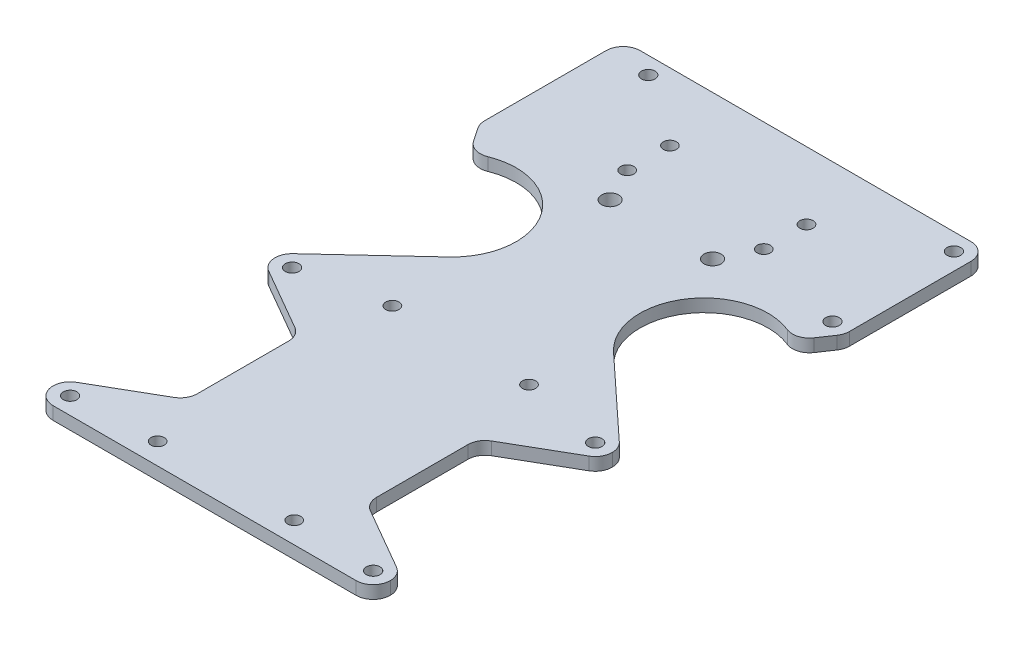
SolidWorks part; units mm, degrees
material "Thornel Mat VMA"
ref_plane "Front Plane" through (0, 0, 0) normal (0, 0, 1) x (1, 0, 0)
ref_plane "Top Plane" through (0, 0, 0) normal (0, 1, 0) x (1, 0, 0)
ref_plane "Right Plane" through (0, 0, 0) normal (1, 0, 0) x (0, 0, -1)
sketch "Sketch1" plane through (0, 0, 0) normal (0, 1, 0) x (1, 0, 0)
  line L0 (0, 0) -> (0, -82.5) construction
  line L1 (29.5, 0) -> (0, 0) construction
  line L19 (16, -27.5) -> (-16, -27.5) construction
  line L22 (16, -27.5) -> (16, 27.5) construction
  line L25 (16, 27.5) -> (-16, 27.5) construction
  line L28 (-16, -27.5) -> (-16, 27.5) construction
  line L38 (16, -27.5) -> (-16, 27.5) construction
  line L41 (47.5, 62.5) -> (-47.5, 62.5)
  line L44 (47.5, 62.5) -> (47.5, -87.5)
  line L47 (47.5, -87.5) -> (-47.5, -87.5)
  line L50 (-47.5, 62.5) -> (-47.5, -87.5)
  line L59 (-959, -57) -> (49041, -57) construction
  line L65 (16, 27.5) -> (-16, -27.5) construction
  line L66 (-16, 37.5) -> (16, 37.5) construction
  line L67 (-16, 37.5) -> (-16, 27.5) construction
  line L69 (16, 37.5) -> (16, 27.5) construction
  line L74 (-16, -27.5) -> (-16, -82.5) construction
  line L75 (-16, -82.5) -> (16, -82.5) construction
  line L76 (16, -82.5) -> (16, -27.5) construction
  line L94 (0, -82.5) -> (0, -87.5) construction
  circle A0 centre (29.5, 0) radius 15
  circle A22 centre (16, 27.5) radius 1.55
  circle A23 centre (16, -27.5) radius 1.55
  circle A24 centre (-16, -27.5) radius 1.55
  circle A25 centre (-16, 27.5) radius 1.55
  circle A76 centre (-16, 37.5) radius 1.55
  circle A77 centre (16, 37.5) radius 1.55
  circle A91 centre (-16, -82.5) radius 1.55
  circle A92 centre (16, -82.5) radius 1.55
  circle A99 centre (-29.5, 0) radius 15
  point P1 (0, -53.5)
  point P37 (29.5, 0)
  point P51 (0, 32.5)
  dimension "D1" = 30
  dimension "D6" = 25
  dimension "D7" = 5
  dimension "D10" = 3.1
  dimension "D12" = 55
  dimension "D15" = 10
  dimension "D19" = 32
  dimension "D20" = 29.5
  dimension "D3" = 95
  dimension "D14" = 55
extrude "凸台-拉伸1" add sketch "Sketch1" along normal blind 3 contours L41 L50 L47 L44 A23 A22 A0 region at (0, 0, 13.8891)
sketch "草图9" plane through (0, 0, 0) normal (0, 1, 0) x (1, 0, 0)
  line L0 (0, 35) -> (0, 0) construction
  line L1 (42.55, 7.5) -> (-42.55, 7.5) construction
  line L2 (42.55, 7.5) -> (42.55, 62.5) construction
  line L3 (42.55, 62.5) -> (-42.55, 62.5) construction
  line L4 (-42.55, 7.5) -> (-42.55, 62.5) construction
  line L5 (42.55, 7.5) -> (-42.55, 62.5) construction
  line L6 (42.55, 62.5) -> (-42.55, 7.5) construction
  line L7 (-32.84, 49.29) -> (38.74, 49.29) construction
  line L8 (38.74, 49.29) -> (38.74, 20.84) construction
  circle A0 centre (-16, 27.5) radius 1.55 construction
  circle A1 centre (38.74, 20.84) radius 1.6
  circle A2 centre (38.74, 49.29) radius 1.6
  circle A3 centre (-32.84, 49.29) radius 1.6
  point P0 (0, 35)
  dimension "D6" = 3.2
  dimension "D1" = 55
  dimension "D2" = 85.1
  dimension "D3" = 20
  dimension "D4" = 3.81
  dimension "D5" = 13.21
  dimension "D7" = 13.34
  dimension "D8" = 9.71
extrude "主控板固定孔" cut sketch "草图9" along normal up to next
sketch "草图10" plane through (0, 0, 0) normal (0, 1, 0) x (1, 0, 0)
  line L0 (0, 0) -> (0, -57.5) construction
  line L1 (35.5, -83.5) -> (-35.5, -83.5) construction
  line L2 (35.5, -83.5) -> (35.5, -31.5) construction
  line L3 (35.5, -31.5) -> (-35.5, -31.5) construction
  line L4 (-35.5, -83.5) -> (-35.5, -31.5) construction
  line L5 (35.5, -83.5) -> (-35.5, -31.5) construction
  line L6 (35.5, -31.5) -> (-35.5, -83.5) construction
  line L7 (47.5, -87.5) -> (-47.5, -87.5) construction
  circle A0 centre (35.5, -31.5) radius 1.6
  circle A1 centre (35.5, -83.5) radius 1.6
  circle A2 centre (-35.5, -31.5) radius 1.6
  circle A3 centre (-35.5, -83.5) radius 1.6
  point P0 (0, -57.5)
  dimension "D1" = 4
  dimension "D2" = 3.2
  dimension "D3" = 52
  dimension "D4" = 71
extrude "图传固定孔" cut sketch "草图10" along normal up to next
sketch "草图11" plane through (0, 0, 0) normal (0, 1, 0) x (1, 0, 0)
  line L0 (0, 0) -> (0, 22.5) construction
  line L1 (9, -22.5) -> (-9, -22.5) construction
  line L2 (9, -22.5) -> (9, 22.5) construction
  line L3 (9, 22.5) -> (-9, 22.5) construction
  line L4 (-9, -22.5) -> (-9, 22.5) construction
  line L5 (9, -22.5) -> (-9, 22.5) construction
  line L6 (9, 22.5) -> (-9, -22.5) construction
  circle A0 centre (-29.5, 0) radius 22.5 construction
  circle A1 centre (-16, 27.5) radius 1.55 construction
  circle A2 centre (-12, 19.5) radius 2
  circle A3 centre (12, 19.5) radius 2
  point P3 (0, 0)
  dimension "D1" = 45
  dimension "D4" = 4
  dimension "D2" = 18
  dimension "D3" = 5
  dimension "D5" = 3
  dimension "D6" = 3
extrude "光电二极管留孔" cut sketch "草图11" along normal up to next
sketch "草图8" plane through (0, 0, 0) normal (0, 1, 0) x (1, 0, 0)
  line L3 (47.5, 62.5) -> (47.5, -87.5)
  line L13 (0, 62.5) -> (0, -87.5) construction
  line L14 (0, 62.5) -> (0, 53.29)
  line L15 (47.5, 62.5) -> (-47.5, 62.5) construction
  line L16 (47.5, -87.5) -> (-47.5, -87.5) construction
  line L17 (0, 62.5) -> (47.5, 62.5)
  line L18 (0, 53.29) -> (42.74, 53.29)
  line L20 (42.74, 53.29) -> (42.74, 19.6164)
  line L23 (39.5, -29.7557) -> (39.5, -33.8094)
  line L27 (47.5, -87.5) -> (39.5, -87.5)
  line L28 (42.74, 19.6164) -> (29.5, 0)
  line L32 (19.2931, -10.9918) -> (39.5, -29.7557)
  line L37 (39.5, -33.8094) -> (21, -44.4904)
  line L38 (21, -44.4904) -> (21, -70.5096)
  line L39 (21, -70.5096) -> (39.5, -81.1906)
  line L40 (21, -57.5) -> (-1.5333, -57.5) construction
  line L41 (-1.5333, -57.5) -> (21, -44.4904) construction
  line L42 (21, -70.5096) -> (-1.5333, -57.5) construction
  line L43 (39.5, -81.1906) -> (39.5, -87.5)
  line L44 (29.5, 0) -> (19.2931, -10.9918)
  circle A0 centre (16, -82.5) radius 1.55 construction
  circle A2 centre (38.74, 49.29) radius 1.6 construction
  circle A3 centre (38.74, 20.84) radius 1.6 construction
  circle A4 centre (29.5, 0) radius 15 construction
  circle A5 centre (35.5, -83.5) radius 1.6 construction
  circle A6 centre (35.5, -31.5) radius 1.6 construction
  dimension "D1" = 4
  dimension "D2" = 4
  dimension "D3" = 4
  dimension "D4" = 4
  dimension "D6" = 4
  dimension "D7" = 5
  dimension "D5" = 4
  dimension "D8" = 60
  dimension "D9" = 4
extrude "板型" cut sketch "草图8" along normal up to next contours L17 L3 L27 L43 L39 L38 L37 L23 L32 L44 L28 L20 L18 L14
mirror "镜向1" about plane through (0, 0, 0) normal (1, 0, 0) of "板型"
fillet "圆角1" radius 4 18 edges at (-39.5, 1.5, 29.7557) (-37.8916, 1.5, -12.433) (-42.74, 1.5, -19.6164) (-42.74, 1.5, -53.29) (42.74, 1.5, -53.29) (42.74, 1.5, -19.6164) (37.8916, 1.5, -12.433) (39.5, 1.5, 29.7557) (-39.5, 1.5, 81.1906) (-21, 1.5, 70.5096) (-21, 1.5, 44.4904) (-39.5, 1.5, 33.8094) (39.5, 1.5, 33.8094) (21, 1.5, 44.4904) (21, 1.5, 70.5096) (39.5, 1.5, 81.1906) (39.5, 1.5, 87.5) (-39.5, 1.5, 87.5)
